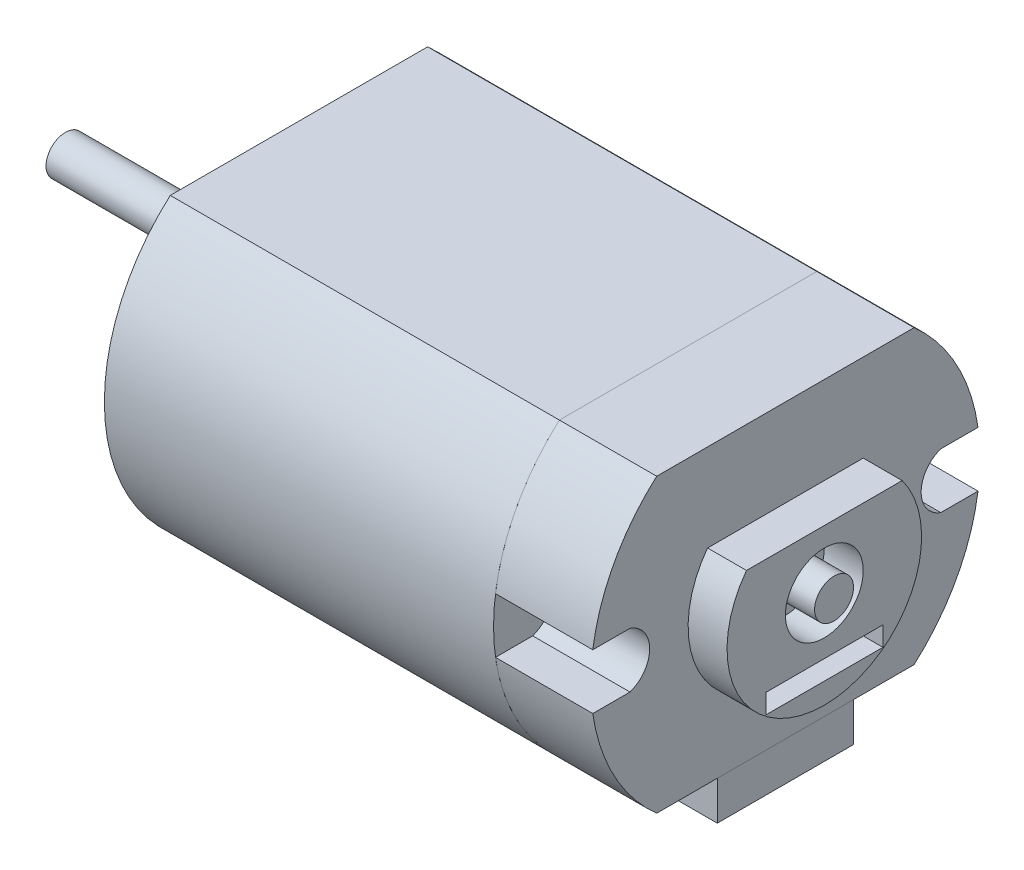
SolidWorks part; units mm, degrees
note: The reader was unsure of these and kept them because the rebuilt part matched: shared geometry of "Sketch3<6>", "Sketch3<7>", "Sketch4<3>".
ref_plane "Front Plane" through (0, 0, 0) normal (0, 0, 1) x (1, 0, 0)
ref_plane "Top Plane" through (0, 0, 0) normal (0, 1, 0) x (1, 0, 0)
ref_plane "Right Plane" through (0, 0, 0) normal (1, 0, 0) x (0, 0, -1)
sketch "Sketch1" plane through (0, 0, 0) normal (1, 0, 0) x (0, 0, -1)
  line L1 (-6.6144, -7.5) -> (6.6144, -7.5)
  line L3 (-6.6144, 7.5) -> (6.6144, 7.5)
  line L5 (-8, -6) -> (8, 6) construction
  line L6 (-8, 6) -> (8, -6) construction
  arc A0 (-6.6144, 7.5) -> (-6.6144, -7.5) centre (0, 0) ccw
  arc A1 (6.6144, -7.5) -> (6.6144, 7.5) centre (0, 0) ccw
  dimension "D1" = 20
extrude "Boss-Extrude1" add sketch "Sketch1" against normal blind 12.5 and the other way blind 7.5
sketch "Sketch2" plane through (7.5, 0, 0) normal (1, 0, 0) x (0, 0, -1)
  line L0 (-6.6144, 7.5) -> (6.6144, 7.5)
  line L1 (6.6144, -7.5) -> (-6.6144, -7.5)
  line L2 (7.987, -1.4182) -> (9.8989, -1.4182)
  line L3 (0, 7.5) -> (0, -7.5) construction
  line L4 (7.987, 1.4182) -> (9.8989, 1.4182)
  line L6 (-7.987, 1.4182) -> (-9.8989, 1.4182)
  line L7 (-7.987, -1.4182) -> (-9.8989, -1.4182)
  arc A0 (-7.987, -1.4182) -> (-7.987, 1.4182) centre (-8.4756, 0) ccw
  arc A1 (6.6144, 7.5) -> (9.8989, 1.4182) centre (0, 0) cw
  arc A2 (-6.6144, -7.5) -> (-9.8989, -1.4182) centre (0, 0) cw
  arc A3 (-9.8989, 1.4182) -> (-6.6144, 7.5) centre (0, 0) cw
  arc A4 (7.987, -1.4182) -> (7.987, 1.4182) centre (8.4756, 0) cw
  arc A5 (9.8989, -1.4182) -> (6.6144, -7.5) centre (0, 0) cw
  dimension "D2" = 1.5
extrude "Boss-Extrude2" add sketch "Sketch2" along normal blind 5 separate body
sketch "Sketch3" plane through (12.5, 0, 0) normal (1, 0, 0) x (0, 0, -1)
  line L0 (0, -7.5) -> (0, -9.5) construction
  line L1 (-4, 3) -> (4, 3)
  line L2 (-2.9878, -3.927) -> (3.0122, -3.927)
  line L3 (-2.9878, -3.927) -> (-2.9878, -2.927)
  line L4 (-2.9878, -2.927) -> (3.0122, -2.927)
  line L5 (3.0122, -3.927) -> (3.0122, -2.927)
  line L8 (-6.6144, -7.5) -> (6.6144, -7.5) construction
  line L10 (-3.5, -9.5) -> (3.5, -9.5)
  line L11 (-3.5, -9.5) -> (-3.5, -7.5)
  line L12 (-3.5, -7.5) -> (3.5, -7.5)
  line L13 (3.5, -9.5) -> (3.5, -7.5)
  arc A0 (-4, 3) -> (4, 3) centre (0, 0) ccw
  circle A1 centre (0, 0) radius 1
  circle A2 centre (0, 0) radius 2
  point P6 (0.0122, -3.427)
  point P15 (0, -8.5)
  point P20 (0, 0)
  point P21 (0, 0)
  dimension "D1" = 10
  dimension "D2" = 2
  dimension "D3" = 4
  dimension "D4" = 6
  dimension "D5" = 1
  dimension "D6" = 7
  dimension "D7" = 2
extrude "Boss-Extrude3" add sketch "Sketch3" along normal blind 2.5 separate body contours A1
extrude "Boss-Extrude6" add sketch "Sketch3<6>" along normal blind 2 separate body contours L4 L5 L2 L3 | A2 | A0 L1
sketch "Sketch3<6>" plane through (12.5, 0, 0) normal (1, 0, 0) x (0, 0, -1) same geometry as "Sketch3"
extrude "Boss-Extrude7" add sketch "Sketch3<7>" against normal blind 5 separate body contours L11 L12 L13 L10
sketch "Sketch3<7>" plane through (12.5, 0, 0) normal (1, 0, 0) x (0, 0, -1) same geometry as "Sketch3"
sketch "Sketch4" plane through (-12.5, 0, 0) normal (-1, 0, 0) x (0, 0, 1)
  circle A0 centre (0, 0) radius 3
  circle A1 centre (0, 0) radius 1
  dimension "D1" = 2
  dimension "D2" = 6
extrude "Boss-Extrude9" add sketch "Sketch4" along normal blind 12 separate body contours A1
extrude "Boss-Extrude10" add sketch "Sketch4<3>" along normal blind 2 contours A1 | A0
sketch "Sketch4<3>" plane through (-12.5, 0, 0) normal (-1, 0, 0) x (0, 0, 1) same geometry as "Sketch4"
